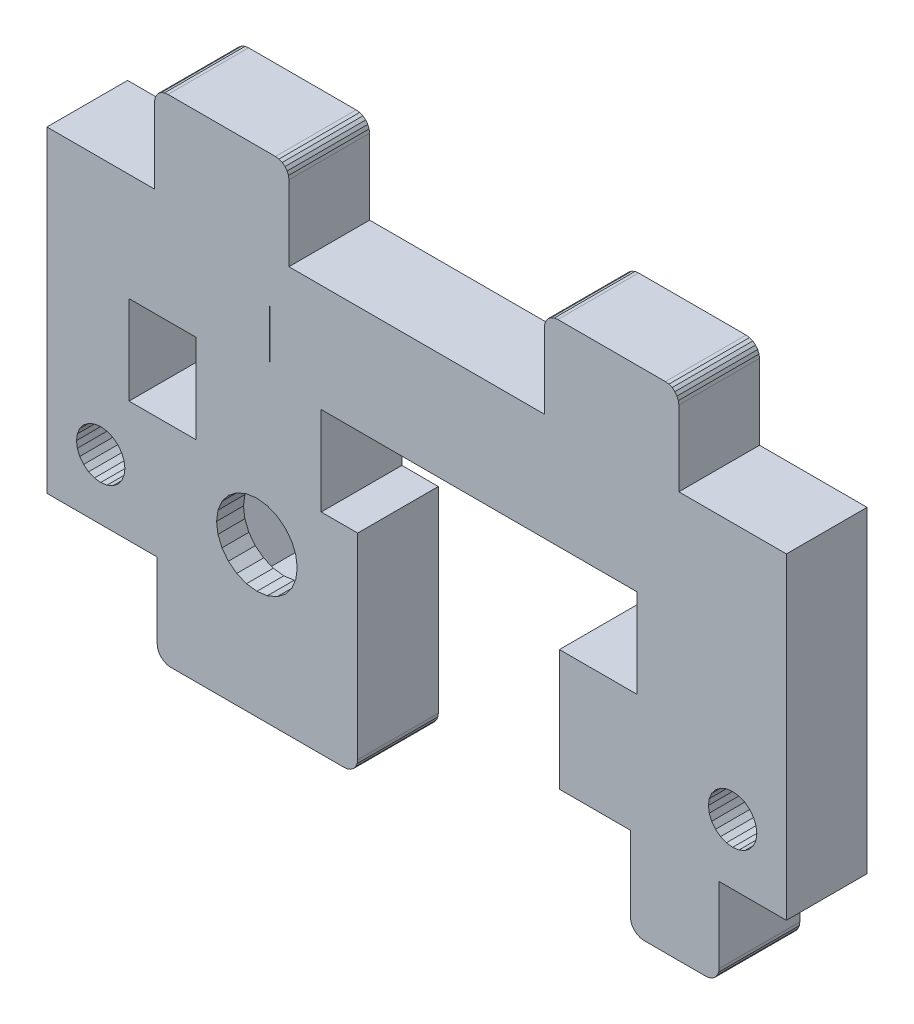
SolidWorks part; units mm, degrees
material "Maple"
ref_plane "Front Plane" through (0, 0, 0) normal (0, 0, 1) x (1, 0, 0)
ref_plane "Top Plane" through (0, 0, 0) normal (0, 1, 0) x (1, 0, 0)
ref_plane "Right Plane" through (0, 0, 0) normal (1, 0, 0) x (0, 0, -1)
sketch "Sketch1" plane through (0, 0, 0) normal (0, 0, 1) x (1, 0, 0)
  line L978 (-432.6066, -186.3004) -> (-433.2279, -185.8236)
  line L979 (-436.8492, -190.543) -> (-436.2279, -191.0198)
  line L980 (-437.326, -189.9217) -> (-436.8492, -190.543)
  line L981 (-433.9515, -185.5239) -> (-434.7279, -185.4217)
  line L982 (-433.9515, -191.3195) -> (-433.2279, -191.0198)
  line L983 (-427.526, -199.2288) -> (-427.3671, -199.0217)
  line L984 (-400.3454, -198.5217) -> (-400.3454, -192.9217)
  line L985 (-432.4793, -163.2217) -> (-432.6383, -163.0146)
  line L986 (-432.6383, -163.0146) -> (-432.8454, -162.8557)
  line L987 (-432.8454, -162.8557) -> (-433.0866, -162.7558)
  line L988 (-441.6042, -162.7558) -> (-441.3454, -162.7217)
  line L989 (-403.8454, -162.8557) -> (-404.0866, -162.7558)
  line L990 (-428.2331, -199.5217) -> (-441.1454, -199.5217)
  line L991 (-428.2331, -199.5217) -> (-427.9743, -199.4876)
  line L992 (-427.9743, -199.4876) -> (-427.7331, -199.3877)
  line L993 (-427.7331, -199.3877) -> (-427.526, -199.2288)
  line L994 (-427.3671, -199.0217) -> (-427.2672, -198.7805)
  line L995 (-427.2672, -198.7805) -> (-427.2331, -198.5217)
  line L996 (-427.2331, -198.5217) -> (-427.2331, -183.9217)
  line L997 (-427.2331, -183.9217) -> (-429.9454, -183.9217)
  line L998 (-429.9454, -183.9217) -> (-429.9454, -177.3217)
  line L999 (-429.9454, -177.3217) -> (-406.4454, -177.3217)
  line L1000 (-406.4454, -177.3217) -> (-406.4454, -183.9217)
  line L1001 (-406.4454, -183.9217) -> (-412.2279, -183.9217)
  line L1002 (-412.2279, -192.9217) -> (-412.2279, -183.9217)
  line L1003 (-406.9454, -192.9217) -> (-412.2279, -192.9217)
  line L1004 (-406.9454, -198.5217) -> (-406.9454, -192.9217)
  line L1005 (-406.9454, -198.5217) -> (-406.9113, -198.7805)
  line L1006 (-406.9113, -198.7805) -> (-406.8114, -199.0217)
  line L1007 (-406.8114, -199.0217) -> (-406.6525, -199.2288)
  line L1008 (-406.6525, -199.2288) -> (-406.4454, -199.3877)
  line L1009 (-406.4454, -199.3877) -> (-406.2042, -199.4876)
  line L1010 (-406.2042, -199.4876) -> (-405.9454, -199.5217)
  line L1011 (-401.3454, -199.5217) -> (-405.9454, -199.5217)
  line L1012 (-401.0866, -199.4876) -> (-401.3454, -199.5217)
  line L1013 (-400.8454, -199.3877) -> (-401.0866, -199.4876)
  line L1014 (-400.6383, -199.2288) -> (-400.8454, -199.3877)
  line L1015 (-400.4793, -199.0217) -> (-400.6383, -199.2288)
  line L1016 (-400.3794, -198.7805) -> (-400.4793, -199.0217)
  line L1017 (-400.3454, -198.5217) -> (-400.3794, -198.7805)
  line L1018 (-400.3454, -192.9217) -> (-395.3454, -192.9217)
  line L1019 (-395.3454, -169.3217) -> (-395.3454, -192.9217)
  line L1020 (-395.3454, -169.3217) -> (-403.3454, -169.3217)
  line L1021 (-403.3454, -163.7217) -> (-403.3454, -169.3217)
  line L1022 (-403.3454, -163.7217) -> (-403.3794, -163.4629)
  line L1023 (-403.3794, -163.4629) -> (-403.4793, -163.2217)
  line L1024 (-403.4793, -163.2217) -> (-403.6383, -163.0146)
  line L1025 (-403.6383, -163.0146) -> (-403.8454, -162.8557)
  line L1026 (-404.0866, -162.7558) -> (-404.3454, -162.7217)
  line L1027 (-412.3454, -162.7217) -> (-404.3454, -162.7217)
  line L1028 (-412.3454, -162.7217) -> (-412.6042, -162.7558)
  line L1029 (-412.6042, -162.7558) -> (-412.8454, -162.8557)
  line L1030 (-412.8454, -162.8557) -> (-413.0525, -163.0146)
  line L1031 (-413.0525, -163.0146) -> (-413.2114, -163.2217)
  line L1032 (-413.2114, -163.2217) -> (-413.3113, -163.4629)
  line L1033 (-413.3113, -163.4629) -> (-413.3454, -163.7217)
  line L1034 (-413.3454, -163.7217) -> (-413.3454, -169.3217)
  line L1035 (-413.3454, -169.3217) -> (-432.3454, -169.3217)
  line L1036 (-432.3454, -169.3217) -> (-432.3454, -163.7217)
  line L1037 (-432.3454, -163.7217) -> (-432.3794, -163.4629)
  line L1038 (-432.3794, -163.4629) -> (-432.4793, -163.2217)
  line L1039 (-433.0866, -162.7558) -> (-433.3454, -162.7217)
  line L1040 (-441.3454, -162.7217) -> (-433.3454, -162.7217)
  line L1041 (-441.8454, -162.8557) -> (-441.6042, -162.7558)
  line L1042 (-442.0525, -163.0146) -> (-441.8454, -162.8557)
  line L1043 (-442.2114, -163.2217) -> (-442.0525, -163.0146)
  line L1044 (-442.3113, -163.4629) -> (-442.2114, -163.2217)
  line L1045 (-442.3454, -163.7217) -> (-442.3113, -163.4629)
  line L1046 (-442.3454, -163.7217) -> (-442.3454, -169.3217)
  line L1047 (-442.3454, -169.3217) -> (-450.3454, -169.3217)
  line L1048 (-450.3454, -192.9217) -> (-450.3454, -169.3217)
  line L1049 (-442.1454, -192.9217) -> (-450.3454, -192.9217)
  line L1050 (-442.1454, -192.9217) -> (-442.1454, -198.5217)
  line L1051 (-442.1454, -198.5217) -> (-442.1113, -198.7805)
  line L1052 (-442.1113, -198.7805) -> (-442.0114, -199.0217)
  line L1053 (-442.0114, -199.0217) -> (-441.8525, -199.2288)
  line L1054 (-441.8525, -199.2288) -> (-441.6454, -199.3877)
  line L1055 (-441.6454, -199.3877) -> (-441.4042, -199.4876)
  line L1056 (-441.4042, -199.4876) -> (-441.1454, -199.5217)
  line L1057 (-439.2402, -183.9217) -> (-439.2454, -177.3217)
  line L1058 (-444.2402, -183.9256) -> (-439.2402, -183.9217)
  line L1059 (-444.2454, -177.3256) -> (-444.2402, -183.9256)
  line L1060 (-439.2454, -177.3217) -> (-444.2454, -177.3256)
  line L1061 (-447.2454, -186.8629) -> (-447.6182, -187.1489)
  line L1062 (-446.8112, -186.683) -> (-447.2454, -186.8629)
  line L1063 (-446.3454, -186.6217) -> (-446.8112, -186.683)
  line L1064 (-445.8795, -186.683) -> (-446.3454, -186.6217)
  line L1065 (-445.4454, -186.8629) -> (-445.8795, -186.683)
  line L1066 (-445.0726, -187.1489) -> (-445.4454, -186.8629)
  line L1067 (-444.7865, -187.5217) -> (-445.0726, -187.1489)
  line L1068 (-444.6067, -187.9558) -> (-444.7865, -187.5217)
  line L1069 (-444.5454, -188.4217) -> (-444.6067, -187.9558)
  line L1070 (-444.6067, -188.8876) -> (-444.5454, -188.4217)
  line L1071 (-444.7865, -189.3217) -> (-444.6067, -188.8876)
  line L1072 (-445.0726, -189.6945) -> (-444.7865, -189.3217)
  line L1073 (-445.4454, -189.9806) -> (-445.0726, -189.6945)
  line L1074 (-445.8795, -190.1604) -> (-445.4454, -189.9806)
  line L1075 (-446.3454, -190.2217) -> (-445.8795, -190.1604)
  line L1076 (-446.8112, -190.1604) -> (-446.3454, -190.2217)
  line L1077 (-447.2454, -189.9806) -> (-446.8112, -190.1604)
  line L1078 (-447.6182, -189.6945) -> (-447.2454, -189.9806)
  line L1079 (-447.9042, -189.3217) -> (-447.6182, -189.6945)
  line L1080 (-448.084, -188.8876) -> (-447.9042, -189.3217)
  line L1081 (-448.1454, -188.4217) -> (-448.084, -188.8876)
  line L1082 (-448.084, -187.9558) -> (-448.1454, -188.4217)
  line L1083 (-447.9042, -187.5217) -> (-448.084, -187.9558)
  line L1084 (-447.6182, -187.1489) -> (-447.9042, -187.5217)
  line L1085 (-400.6182, -187.1489) -> (-400.9042, -187.5217)
  line L1086 (-400.2454, -186.8629) -> (-400.6182, -187.1489)
  line L1087 (-399.8112, -186.683) -> (-400.2454, -186.8629)
  line L1088 (-399.3454, -186.6217) -> (-399.8112, -186.683)
  line L1089 (-398.8795, -186.683) -> (-399.3454, -186.6217)
  line L1090 (-398.4454, -186.8629) -> (-398.8795, -186.683)
  line L1091 (-398.0726, -187.1489) -> (-398.4454, -186.8629)
  line L1092 (-397.7865, -187.5217) -> (-398.0726, -187.1489)
  line L1093 (-397.6067, -187.9558) -> (-397.7865, -187.5217)
  line L1094 (-397.5454, -188.4217) -> (-397.6067, -187.9558)
  line L1095 (-397.6067, -188.8876) -> (-397.5454, -188.4217)
  line L1096 (-397.7865, -189.3217) -> (-397.6067, -188.8876)
  line L1097 (-398.0726, -189.6945) -> (-397.7865, -189.3217)
  line L1098 (-398.4454, -189.9806) -> (-398.0726, -189.6945)
  line L1099 (-398.8795, -190.1604) -> (-398.4454, -189.9806)
  line L1100 (-399.3454, -190.2217) -> (-398.8795, -190.1604)
  line L1101 (-399.8112, -190.1604) -> (-399.3454, -190.2217)
  line L1102 (-400.2454, -189.9806) -> (-399.8112, -190.1604)
  line L1103 (-400.6182, -189.6945) -> (-400.2454, -189.9806)
  line L1104 (-400.9042, -189.3217) -> (-400.6182, -189.6945)
  line L1105 (-401.084, -188.8876) -> (-400.9042, -189.3217)
  line L1106 (-401.1454, -188.4217) -> (-401.084, -188.8876)
  line L1107 (-401.084, -187.9558) -> (-401.1454, -188.4217)
  line L1108 (-400.9042, -187.5217) -> (-401.084, -187.9558)
  line L1109 (-437.3081, -192.9341) -> (-432.112, -192.9341)
  line L1110 (-439.9062, -188.4341) -> (-437.3081, -192.9341)
  line L1111 (-437.3081, -183.9341) -> (-439.9062, -188.4341)
  line L1112 (-432.112, -183.9341) -> (-437.3081, -183.9341)
  line L1113 (-429.5139, -188.4341) -> (-432.112, -183.9341)
  line L1114 (-432.112, -192.9341) -> (-429.5139, -188.4341)
  line L1115 (-431.7279, -188.4217) -> (-431.8301, -187.6453)
  line L1116 (-431.8301, -189.1982) -> (-431.7279, -188.4217)
  line L1117 (-433.2279, -191.0198) -> (-432.6066, -190.543)
  line L1118 (-436.2279, -191.0198) -> (-435.5044, -191.3195)
  line L1119 (-437.6257, -189.1982) -> (-437.326, -189.9217)
  line L1120 (-437.7279, -188.4217) -> (-437.6257, -189.1982)
  line L1121 (-437.326, -186.9217) -> (-437.6257, -187.6453)
  line L1122 (-436.8492, -186.3004) -> (-437.326, -186.9217)
  line L1123 (-435.5044, -185.5239) -> (-436.2279, -185.8236)
  line L1124 (-434.7279, -185.4217) -> (-435.5044, -185.5239)
  line L1125 (-432.2274, -192.7341) -> (-429.7448, -188.4341)
  line L1126 (-429.7448, -188.4341) -> (-432.2274, -184.1341)
  line L1127 (-432.2274, -184.1341) -> (-437.1927, -184.1341)
  line L1128 (-437.1927, -184.1341) -> (-439.6753, -188.4341)
  line L1129 (-439.6753, -188.4341) -> (-437.1927, -192.7341)
  line L1130 (-437.1927, -192.7341) -> (-432.2274, -192.7341)
  line L1131 (-437.0772, -192.5341) -> (-432.3429, -192.5341)
  line L1132 (-432.3429, -192.5341) -> (-429.9758, -188.4341)
  line L1133 (-429.9758, -188.4341) -> (-432.3429, -184.3341)
  line L1134 (-432.3429, -184.3341) -> (-437.0772, -184.3341)
  line L1135 (-437.0772, -184.3341) -> (-439.4443, -188.4341)
  line L1136 (-439.4443, -188.4341) -> (-437.0772, -192.5341)
  line L1137 (-436.9617, -192.3341) -> (-432.4584, -192.3341)
  line L1138 (-432.4584, -192.3341) -> (-430.2067, -188.4341)
  line L1139 (-430.2067, -188.4341) -> (-432.4584, -184.5341)
  line L1140 (-432.4584, -184.5341) -> (-436.9617, -184.5341)
  line L1141 (-436.9617, -184.5341) -> (-439.2134, -188.4341)
  line L1142 (-439.2134, -188.4341) -> (-436.9617, -192.3341)
  line L1143 (-436.8462, -184.7341) -> (-438.9824, -188.4341)
  line L1144 (-438.9824, -188.4341) -> (-436.8462, -192.1341)
  line L1145 (-436.8462, -192.1341) -> (-432.5739, -192.1341)
  line L1146 (-432.5739, -192.1341) -> (-430.4377, -188.4341)
  line L1147 (-430.4377, -188.4341) -> (-432.5739, -184.7341)
  line L1148 (-432.5739, -184.7341) -> (-436.8462, -184.7341)
  line L1149 (-430.6686, -188.4341) -> (-432.6893, -184.9341)
  line L1150 (-432.6893, -184.9341) -> (-436.7308, -184.9341)
  line L1151 (-436.7308, -184.9341) -> (-438.7515, -188.4341)
  line L1152 (-438.7515, -188.4341) -> (-436.7308, -191.9341)
  line L1153 (-436.7308, -191.9341) -> (-432.6893, -191.9341)
  line L1154 (-432.6893, -191.9341) -> (-430.6686, -188.4341)
  line L1155 (-430.8995, -188.4341) -> (-432.8048, -185.1341)
  line L1156 (-432.8048, -185.1341) -> (-436.6153, -185.1341)
  line L1157 (-436.6153, -185.1341) -> (-438.5206, -188.4341)
  line L1158 (-438.5206, -188.4341) -> (-436.6153, -191.7341)
  line L1159 (-436.6153, -191.7341) -> (-432.8048, -191.7341)
  line L1160 (-432.8048, -191.7341) -> (-430.8995, -188.4341)
  line L1161 (-431.1305, -188.4341) -> (-432.9203, -185.3341)
  line L1162 (-432.9203, -185.3341) -> (-436.4998, -185.3341)
  line L1163 (-436.4998, -185.3341) -> (-438.2896, -188.4341)
  line L1164 (-438.2896, -188.4341) -> (-436.4998, -191.5341)
  line L1165 (-436.4998, -191.5341) -> (-432.9203, -191.5341)
  line L1166 (-432.9203, -191.5341) -> (-431.1305, -188.4341)
  line L1167 (-433.2279, -185.8236) -> (-433.9515, -185.5239)
  line L8346 (-434.7279, -191.4217) -> (-433.9515, -191.3195)
  line L8347 (-432.1298, -186.9217) -> (-432.6066, -186.3004)
  line L8348 (-432.1298, -189.9217) -> (-431.8301, -189.1982)
  line L8349 (-436.2279, -185.8236) -> (-436.8492, -186.3004)
  line L8350 (-432.1298, -186.9217) -> (-431.8301, -187.6453)
  line L8351 (-432.1298, -189.9217) -> (-432.6066, -190.543)
  line L8352 (-434.7279, -191.4217) -> (-435.5044, -191.3195)
  line L8353 (-437.7279, -188.4217) -> (-437.6257, -187.6453)
  line L8815 (-433.7713, -176.1758) -> (-433.7914, -176.272)
  line L8816 (-433.7914, -176.272) -> (-433.8517, -176.3608)
  line L8817 (-433.8517, -176.3608) -> (-434.0929, -176.5161)
  line L8818 (-434.0929, -176.5161) -> (-434.4543, -176.6215)
  line L8819 (-434.4543, -176.6215) -> (-434.8953, -176.6566)
  line L8820 (-434.8953, -176.6566) -> (-435.3362, -176.6215)
  line L8821 (-435.3362, -176.6215) -> (-435.6976, -176.5161)
  line L8822 (-435.6976, -176.5161) -> (-435.9388, -176.3608)
  line L8823 (-435.9388, -176.3608) -> (-435.9991, -176.272)
  line L8824 (-435.9991, -176.272) -> (-436.0192, -176.1758)
  line L8825 (-436.0192, -176.1758) -> (-436.0192, -172.3669)
  line L8826 (-436.0192, -172.3669) -> (-436.0192, -176.1758)
  line L8827 (-436.0192, -176.1758) -> (-435.9991, -176.272)
  line L8828 (-435.9991, -176.272) -> (-435.9388, -176.3608)
  line L8829 (-435.9388, -176.3608) -> (-435.6976, -176.5161)
  line L8830 (-435.6976, -176.5161) -> (-435.3362, -176.6215)
  line L8831 (-435.3362, -176.6215) -> (-434.8953, -176.6566)
  line L8832 (-434.8953, -176.6566) -> (-434.4543, -176.6215)
  line L8833 (-434.4543, -176.6215) -> (-434.0929, -176.5161)
  line L8834 (-434.0929, -176.5161) -> (-433.8517, -176.3608)
  line L8835 (-433.8517, -176.3608) -> (-433.7914, -176.272)
  line L8836 (-433.7914, -176.272) -> (-433.7713, -172.3669)
  line L8837 (-433.7713, -172.3669) -> (-433.7713, -176.1758)
extrude "Boss-Extrude1" add sketch "Sketch1" against normal blind 6 contours L1055 L1056 L990 L991 L992 L993 L983 L994 L995 L996 L997 L998 L999 L1000 L1001 L1002 L1003 L1004 L1005 L1006 L1007 L1008 L1009 L1010 L1011 L1012 L1013 L1014 L1015 L1016 L1017 L984 L1018 L1019 L1020 L1021 L1022 L1023 L1024 L1025 L989 L1026 L1027 L1028 L1029 L1030 L1031 L1032 L1033 L1034 L1035 region at (-428.0324, -198.7833, 0)
extrude "Boss-Extrude2" add sketch "Sketch1<3>" against normal blind 2 contours L1109 L1114 L1113 L1112 L1111 L1110 L1130 L1129 L1128 L1127 L1126 L1125 | L1129 L1130 L1125 L1126 L1127 L1128 L1136 L1135 L1134 L1133 L1132 L1131 | L1135 L1136 L1131 L1132 L1133 L1134 L1142 L1141 L1140 L1139 L1138 L1137 | L1141 L1142 L1137 L1138 L1139 L1140 L1148 L1147 L1146 L1145 L1144 L1143 | L1147 L1148 L1143 L1144 L1145 L1146 L1154 L1153 L1152 L1151 L1150 L1149 | L1153 L1154 L1149 L1150 L1151 L1152 L1160 L1159 L1158 L1157 L1156 L1155 | L1159 L1160 L1155 L1156 L1157 L1158 L1166 L1165 L1164 L1163 L1162 L1161 | L1165 L1166 L1161 L1162 L1163 L1164 L1120 L8353 L1121 L1122 L8349 L1123 L1124 L981 L1167 L978 L8347 L8350 L1115 L1116 L8348 L8351 L1117 L982 L8346 L8352 L1118 L979 L980 L1119 region at (-438.4881, -190.6154, 0) region at (-434.71, -192.6028, 0) region at (-438.1523, -190.4215, 0) region at (-437.9844, -190.3246, 0) region at (-434.71, -184.8472, 0) region at (-431.7716, -190.1307, 0) region at (-431.9395, -190.0337, 0) region at (-432.1074, -189.9368, 0)
sketch "Sketch1<3>" plane through (0, 0, 0) normal (0, 0, 1) x (1, 0, 0) same geometry as "Sketch1"
